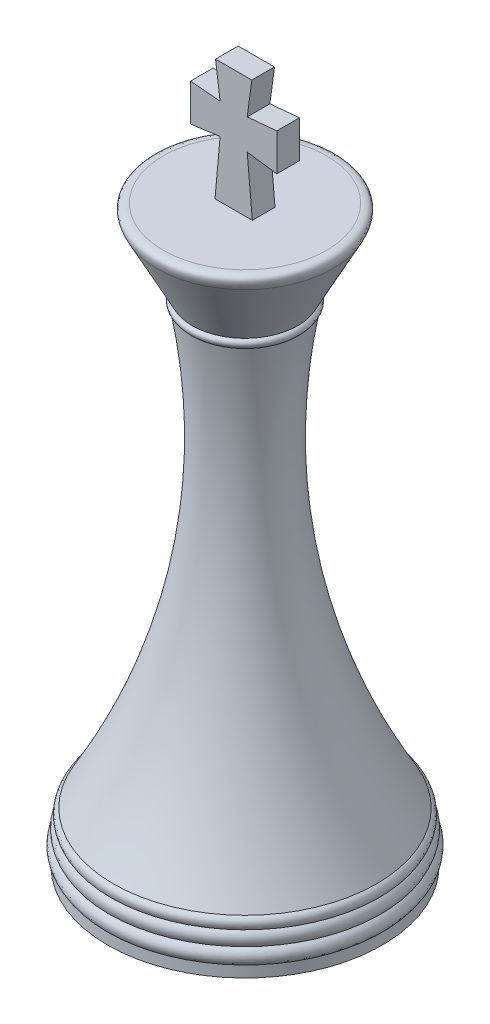
SolidWorks part; units mm, degrees
ref_plane "Front Plane" through (0, 0, 0) normal (0, 0, 1) x (1, 0, 0)
ref_plane "Top Plane" through (0, 0, 0) normal (0, 1, 0) x (1, 0, 0)
ref_plane "Right Plane" through (0, 0, 0) normal (1, 0, 0) x (0, 0, -1)
sketch "Body" plane through (0, 0, 0) normal (0, 0, 1) x (1, 0, 0)
  line L0 (0, 55.2312) -> (0, -52.9675) construction
  line L1 (0, -35.1126) -> (-18.1746, -35.1126)
  line L2 (-18.1746, -35.1126) -> (-18.1746, -33.6224)
  line L3 (-6.991, 30.3446) -> (-11.6211, 39.1907)
  line L4 (-10.8356, 40.922) -> (0, 40.922)
  line L5 (0, 40.922) -> (0, -35.1126)
  spline S0 degree 3 poles (-18.1746, -33.6224) (-18.7468, -32.9387) (-18.6494, -32.2176) (-17.9785, -31.6565) knots 0 0 0 0 1 1 1 1
  spline S1 degree 2 poles (-17.9785, -31.6565) (-18.5653, -30.6179) (-17.7523, -29.8825) knots 0 0 0 1 1 1
  spline S2 degree 2 poles (-17.7523, -29.8825) (-18.2384, -28.9553) (-17.4407, -28.4411) knots 0 0 0 1 1 1
  spline S3 degree 2 poles (-17.4407, -28.4411) (-1.6507, -0.7489) (-7.0234, 29.19) knots 0 0 0 1 1 1
  spline S4 degree 3 poles (-7.0234, 29.19) (-7.5599, 29.7042) (-7.4228, 30.1337) (-6.991, 30.3446) knots 0 0 0 0 1 1 1 1
  spline S5 degree 2 poles (-11.6211, 39.1907) (-12.5762, 40.9904) (-10.8356, 40.922) knots 0 0 0 1 1 1
  point P15 (0, 0)
  point P19 (0, 0)
  point P20 (-5.7027, 11.4801)
sketch "Head" plane through (0, 0, 0) normal (0, 0, 1) x (1, 0, 0)
  line L0 (2.4721, 40.922) -> (-2.4721, 40.922)
  line L2 (-2.4721, 40.922) -> (-1.7935, 48.4075)
  line L3 (-1.7935, 48.4075) -> (-5.7133, 47.8789)
  line L4 (-5.7133, 47.8789) -> (-5.7133, 52.8041)
  line L5 (-5.7133, 52.8041) -> (-1.7935, 52.4487)
  line L6 (-1.7935, 52.4487) -> (-2.4046, 56.9806)
  line L7 (-2.4046, 56.9806) -> (2.4046, 56.9806)
  line L9 (0, 55.2312) -> (0, 38.011) construction
  line L10 (0, 40.922) -> (0, -35.1126) construction
  line L11 (1.7935, 52.4487) -> (2.4046, 56.9806)
  line L12 (5.7133, 52.8041) -> (1.7935, 52.4487)
  line L13 (5.7133, 47.8789) -> (5.7133, 52.8041)
  line L14 (1.7935, 48.4075) -> (5.7133, 47.8789)
  line L15 (2.4721, 40.922) -> (1.7935, 48.4075)
  point P14 (0, 40.922)
  point P15 (0, 56.9806)
revolve "Revolve2" add sketch "Body" angle 360 about L0
extrude "Boss-Extrude1" add sketch "Head" along normal blind 1.5 and the other way blind 1.5
